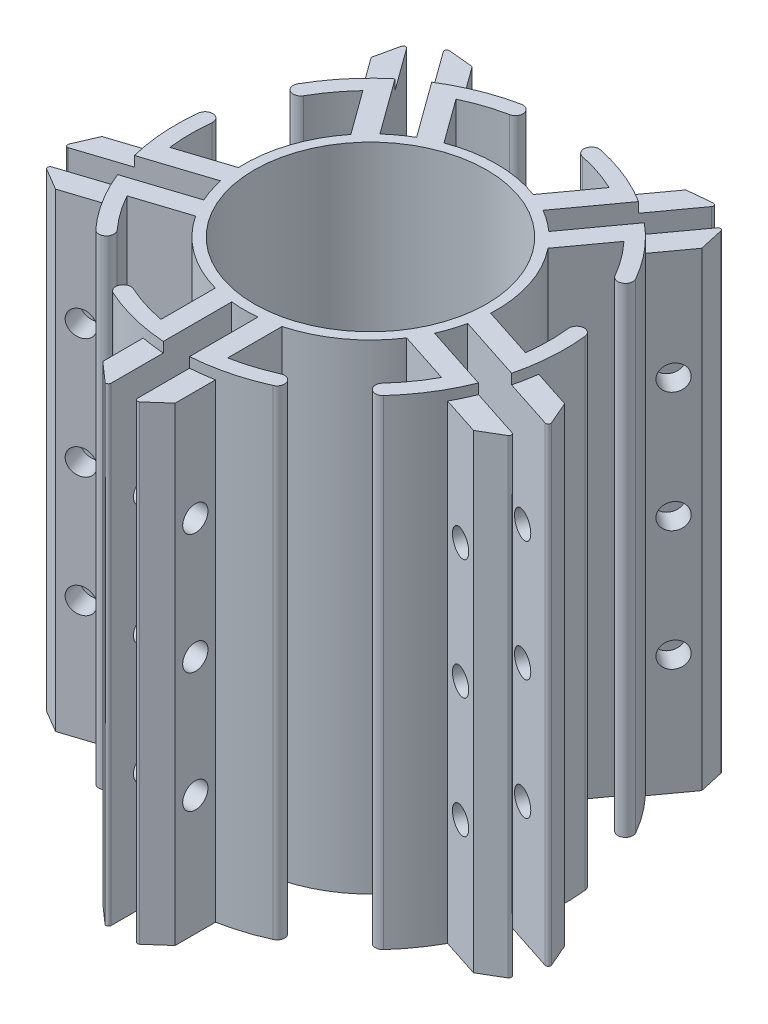
SolidWorks part; units mm, degrees
ref_plane "Front Plane" through (0, 0, 0) normal (0, 0, 1) x (1, 0, 0)
ref_plane "Top Plane" through (0, 0, 0) normal (0, 1, 0) x (1, 0, 0)
ref_plane "Right Plane" through (0, 0, 0) normal (1, 0, 0) x (0, 0, -1)
sketch "Sketch2" plane through (0, 0, 0) normal (0, 1, 0) x (1, 0, 0)
  circle A0 centre (0, 0) radius 29.21
  dimension "D1" = 58.42
sketch "Sketch1" plane through (0, 0, 0) normal (0, 1, 0) x (1, 0, 0)
  line L0 (-20.1089, -44.5685) -> (-18.542, -41.0956) construction
  line L1 (-8.382, -27.9815) -> (-8.382, -44.299)
  line L2 (-9.0903, -48.0426) -> (-9.0903, -58.2026)
  line L3 (-3.302, -63.3128) -> (-3.302, -29.0228)
  line L4 (-9.0903, -58.2026) -> (-3.302, -63.3128)
  line L5 (0, 0) -> (0, -63.3128) construction
  line L6 (20.1089, -44.5685) -> (18.542, -41.0956) construction
  line L7 (9.0903, -58.2026) -> (3.302, -63.3128)
  line L8 (3.302, -63.3128) -> (3.302, -29.0228)
  line L9 (9.0903, -48.0426) -> (9.0903, -58.2026)
  line L10 (8.382, -27.9815) -> (8.382, -44.299)
  circle A0 centre (0, 0) radius 29.21
  arc A1 (-20.1089, -44.5685) -> (-9.0903, -48.0426) centre (0, 0) ccw
  arc A2 (-18.542, -41.0956) -> (-8.382, -44.299) centre (0, 0) ccw
  arc A3 (-20.1089, -44.5685) -> (-9.0903, -48.0426) centre (0, 0) ccw construction
  arc A4 (-20.1089, -44.5685) -> (-18.542, -41.0956) centre (-19.3255, -42.8321) cw
  arc A5 (20.1089, -44.5685) -> (18.542, -41.0956) centre (19.3255, -42.8321) ccw
  arc A6 (18.542, -41.0956) -> (8.382, -44.299) centre (0, 0) cw
  arc A7 (20.1089, -44.5685) -> (9.0903, -48.0426) centre (0, 0) cw
  dimension "D1" = 58.42
  dimension "D6" = 5.08
  dimension "D2" = 48.895
  dimension "D3" = 3.81
  dimension "D4" = 3.302
  dimension "D5" = 10.16
  dimension "D7" = 34.29
  dimension "D8" = 10.16
extrude "Extrude-Thin1" add sketch "Sketch2" along normal blind 120.65 thin thin type one direction wall 2.54
extrude "Boss-Extrude1" add sketch "Sketch1" along normal up to surface (120.65 mm away) contours A4 A1 L2 L4 L3 A0 L1 A2 | A7 A5 A6 L10 A0 L8 L7 L9 region at (-7.866, 0, 45.061) region at (7.866, 0, 45.061) up to face at (31.75, 120.65, 0)
sketch "Sketch6" plane through (0, 120.65, 0) normal (0, 1, 0) x (1, 0, 0)
  line L0 (-9.0903, -48.0426) -> (-9.0903, -58.2026) construction
  line L1 (-9.0903, -48.0426) -> (-12.3959, -65.5126)
  line L2 (12.3959, -65.5126) -> (9.0903, -48.0426)
  arc A0 (9.0903, -48.0426) -> (-9.0903, -48.0426) centre (0, 0) cw
  arc A1 (12.3959, -65.5126) -> (-12.3959, -65.5126) centre (0, 0) cw
  dimension "D1" = 17.78
extrude "Cut-Extrude3" cut sketch "Sketch6" against normal blind 2.54
ref_axis "Axis1" through (0, 120.65, 0) along (0, -1, 0)
fillet "Fillet1" radius 0.635 2 edges at (3.302, 59.055, 63.3128) (-3.302, 59.055, 63.3128)
sketch "Sketch3" plane through (9.0903, 0, 0) normal (1, 0, 0) x (0, 0, -1)
  line L0 (48.0426, 120.65) -> (-58.2026, 120.65) construction
  line L1 (-58.2026, 118.11) -> (-48.0426, 118.11) construction
  circle A0 centre (-53.1226, 90.4875) radius 3.175
  circle A1 centre (-53.1226, 60.325) radius 3.175
  circle A2 centre (-53.1226, 30.1625) radius 3.175
  point P10 (-53.1226, 118.11)
  dimension "D3" = 6.35
  dimension "D1" = 30.1625
  dimension "D2" = 30.1625
  dimension "D4" = 30.1625
extrude "Cut-Extrude1" cut sketch "Sketch3" against normal through all
ref_plane "Plane4" through (0, 0, 0) normal (-0.7071, 0, 0.7071) x (0.7071, 0, 0.7071)
pattern_circular "CirPattern1" count 5 over 360 about axis through (0, 120.65, 0) along (0, -1, 0) of "Boss-Extrude1", "Fillet1", "Cut-Extrude1", "Cut-Extrude3"
